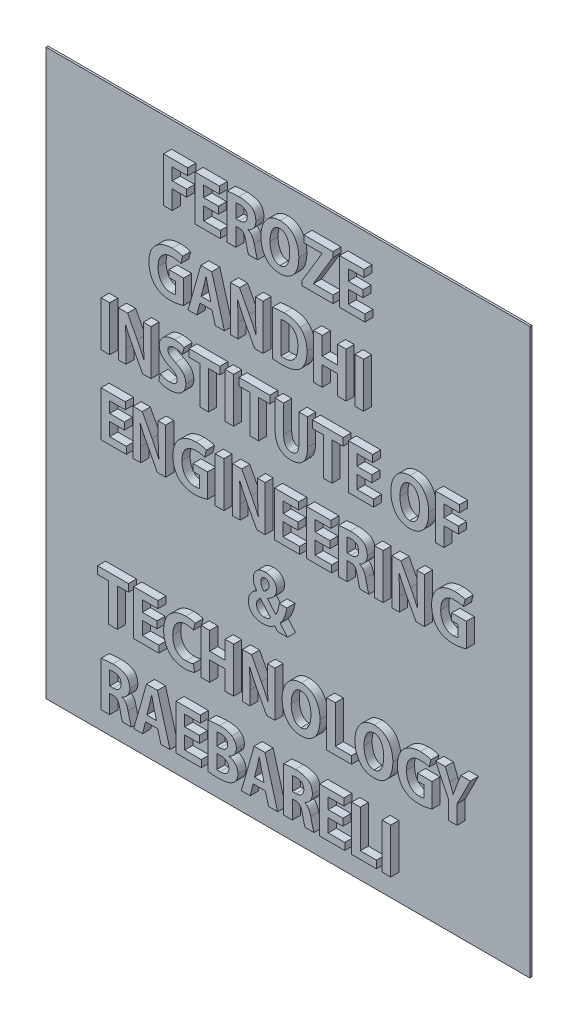
SolidWorks part; units mm, degrees
ref_plane "Front Plane" through (0, 0, 0) normal (0, 0, 1) x (1, 0, 0)
ref_plane "Top Plane" through (0, 0, 0) normal (0, 1, 0) x (1, 0, 0)
ref_plane "Right Plane" through (0, 0, 0) normal (1, 0, 0) x (0, 0, -1)
sketch "Sketch1" plane through (0, 0, 0) normal (0, 0, 1) x (1, 0, 0)
  line L1 (0, 0) -> (120, 0)
  line L2 (0, 0) -> (0, 140)
  line L3 (0, 140) -> (120, 140)
  line L4 (120, 0) -> (120, 140)
  dimension "D1" = 140
  dimension "D2" = 120
extrude "Boss-Extrude1" add sketch "Sketch1" along normal blind 0.5
sketch "Sketch2" plane through (0, 0, 0.5) normal (0, 0, 1) x (1, 0, 0)
  text T0 "        FEROZE \r\n       GANDHI \r\n   INSTITUTE OF \r\n   ENGINEERING\r\n               &\r\n   TECHNOLOGY\r\n   RAEBARELI" font "@Adobe Gothic Std B" height in points 36
extrude "Boss-Extrude2" add sketch "Sketch2" along normal blind 2
